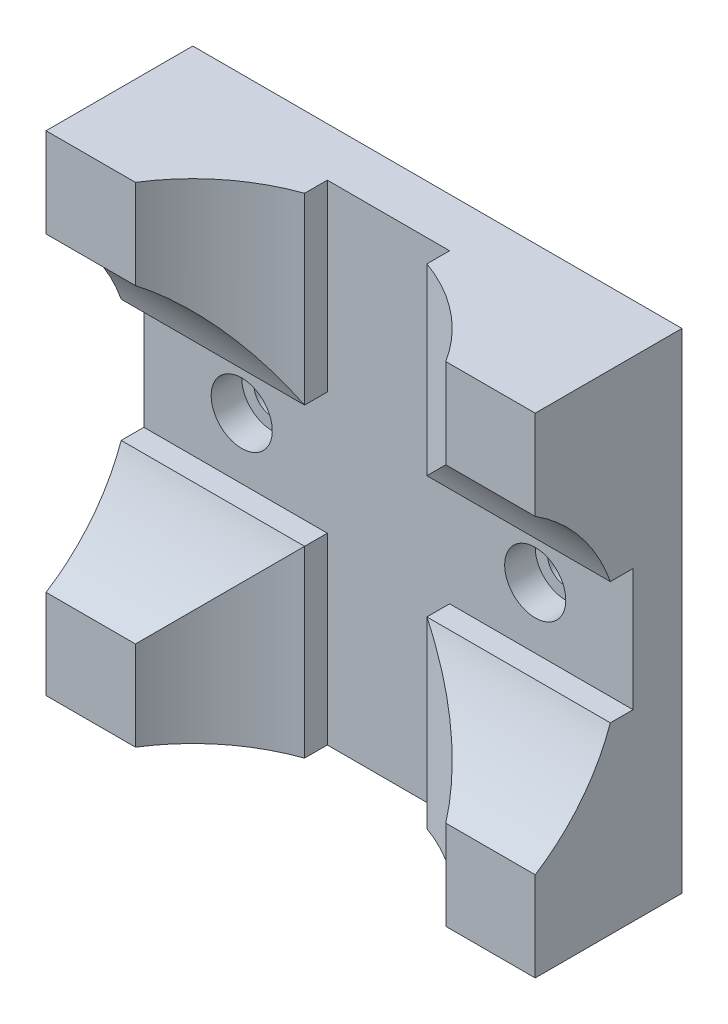
SolidWorks part; units mm, degrees
ref_plane "Front Plane" through (0, 0, 0) normal (0, 0, 1) x (1, 0, 0)
ref_plane "Top Plane" through (0, 0, 0) normal (0, 1, 0) x (1, 0, 0)
ref_plane "Right Plane" through (0, 0, 0) normal (1, 0, 0) x (0, 0, -1)
sketch "Sketch1" plane through (0, 0, 0) normal (0, 0, 1) x (1, 0, 0)
  line L1 (0, 0) -> (40, 0)
  line L2 (0, 0) -> (0, 40)
  line L3 (0, 40) -> (40, 40)
  line L4 (40, 0) -> (40, 40)
  dimension "D1" = 40
  dimension "D2" = 40
extrude "Boss-Extrude1" add sketch "Sketch1" along normal blind 12
ref_plane "Plane1" through (40, 0, 0) normal (1, 0, 0) x (0, 0, -1)
sketch "Sketch2" plane through (40, 0, 0) normal (1, 0, 0) x (0, 0, -1)
  line L0 (-5, 25) -> (-4, 25)
  line L1 (-4, 25) -> (-4, 15)
  line L3 (-5, 15) -> (-5.8579, 15)
  line L5 (-5.8579, 25) -> (-5, 25)
  line L8 (-4, 15) -> (-5, 15)
  arc A0 (-5.8579, 25) -> (-5.8579, 15) centre (-20, 20) ccw
  dimension "D1" = 1
extrude "Cut-Extrude1" cut sketch "Sketch2" against normal blind 40
ref_plane "Plane2" through (0, 0, 0) normal (0, 0, -1) x (-1, 0, 0)
sketch "Sketch3" plane through (0, 0, 0) normal (0, 0, -1) x (-1, 0, 0)
  circle A0 centre (-32, 20) radius 1.5
  circle A1 centre (-8, 20) radius 1.5
  circle A2 centre (-32, 20) radius 2.5
  circle A3 centre (-8, 20) radius 2.5
extrude "Cut-Extrude3" cut sketch "Sketch3" against normal blind 40 contours A2 | A3
extrude "Boss-Extrude3" add sketch "Sketch3<5>" against normal blind 1.5 contours A1 | A0 | A3 | A2
sketch "Sketch3<5>" plane through (0, 0, 0) normal (0, 0, -1) x (-1, 0, 0) same geometry as "Sketch3"
ref_point "Point6"
ref_axis "Axis4" through (20, 20, 4) along (0, 0, 1)
pattern_circular "CirPattern3" count 2 every 90 about axis through (20, 20, 4) along (0, 0, 1) of "Cut-Extrude1"
